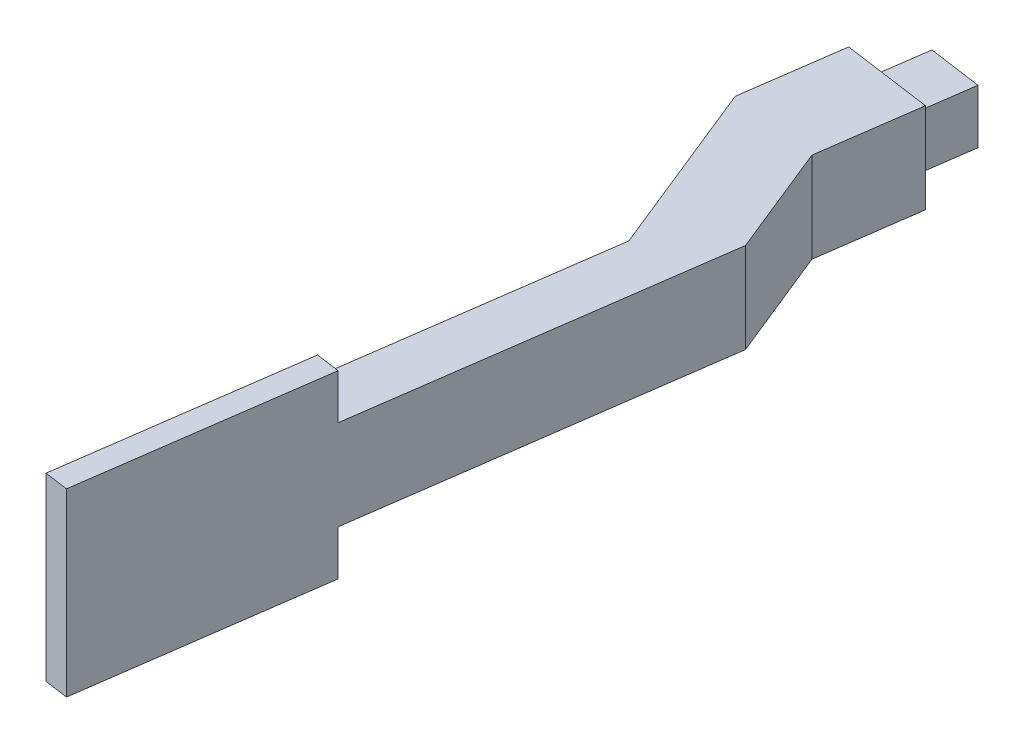
SolidWorks part; units mm, degrees
ref_plane "Plan de face" through (0, 0, 0) normal (0, 0, 1) x (1, 0, 0)
ref_plane "Plan de dessus" through (0, 0, 0) normal (0, 1, 0) x (1, 0, 0)
ref_plane "Plan de droite" through (0, 0, 0) normal (1, 0, 0) x (0, 0, -1)
sketch "Esquisse2" plane through (0, 0, 0) normal (0, 1, 0) x (1, 0, 0)
  circle A0 centre (0, 0) radius 20
  dimension "D1" = 40
extrude "Boss.-Extru.1" add sketch "Esquisse2" along normal blind 5
sketch "Esquisse3" plane through (0, 5, 0) normal (0, 1, 0) x (1, 0, 0)
  line L0 (-1.625, 19.9339) -> (-1.25, 21.9339)
  line L1 (1.25, 21.9339) -> (1.625, 19.9339)
  line L2 (1.625, 19.9339) -> (-1.625, 19.9339)
  line L3 (-1.25, 21.9339) -> (1.25, 21.9339)
  circle A0 centre (0, 0) radius 20 construction
  point P9 (0, 21.9339)
  dimension "2.25" = 2.5
  dimension "D2" = 3.25
  dimension "D3" = 2
extrude "Boss.-Extru.2" add sketch "Esquisse3" against normal blind 5
sketch "Esquisse4" plane through (0, 0, 0) normal (1, 0, 0) x (0, 0, -1)
  line L0 (0, 6.9677) -> (0, -6.1769) construction
  dimension "D1" = 13.1446
ref_plane "Plan1" through (0, 0, 0) normal (0.9903, 0, 0.1392) x (0, -1, 0)
pattern_circular "Répétition circulaire1" count 24 over 360 about axis through (0, 0, 0) along (0, 1, 0) of "Boss.-Extru.2"
hole_wizard "Dégagement M22" positions "Esquisse8" profile "Esquisse9" size "M2" standard "Ansi Metric" slot yes end condition through all
sketch "Esquisse8" plane through (0, 5, 0) normal (0, 1, 0) x (1, 0, 0)
  point P0 (0, 0)
sketch "Esquisse9" plane through (0, 5, 0) normal (1, 0, 0) x (0, 0, 1)
  line L0 (0, 0) -> (0, 5)
  line L1 (0, 5) -> (2.55, 5)
  line L2 (2.55, 5) -> (2.55, 0)
  line L5 (2.55, 0) -> (0, 0)
  line L11 (0, -6.35) -> (0, 107.95) construction
  dimension "Diamètre du perçage jusqu'au prochain" = 5.1
  dimension "Profondeur du perçage jusqu'au prochain" = 5
sketch "Esquisse11" plane through (0, 5, 0) normal (0, 1, 0) x (1, 0, 0)
  line L0 (-5.8011, -14.3321) -> (1.6259, -15.3759)
  line L1 (-5.8011, -14.3321) -> (-7.8887, -29.1861)
  line L2 (1.6259, -15.3759) -> (-0.4617, -30.2299)
  line L3 (-1.895, -44.0211) -> (-7.8887, -29.1861)
  line L4 (-1.0062, -7.1592) -> (1.0062, 7.1592) construction
  line L5 (-0.4617, -30.2299) -> (3.2844, -39.5018)
  line L6 (3.2844, -39.5018) -> (-2.2825, -79.1125)
  line L7 (-2.2825, -79.1125) -> (-6.7388, -78.4862)
  line L8 (-6.7388, -78.4862) -> (-1.895, -44.0211)
  dimension "D1" = 15
  dimension "D2" = 7.5
  dimension "15" = 15
  dimension "D3" = 15
  dimension "D4" = 3.75
  dimension "D5" = 150
  dimension "D6" = 150
  dimension "D7" = 40
  dimension "D8" = 4.5
  dimension "D9" = 5
extrude "Boss.-Extru.3" add sketch "Esquisse11" against normal blind 7.5
sketch "Esquisse13" plane through (3.7135, 0, 0.5219) normal (0.9903, 0, 0.1392) x (0.1392, 0, -0.9903)
  line L1 (-21.6382, 26.561) -> (35.5681, 26.561)
  line L2 (-21.6382, 26.561) -> (-21.6382, -11.2376)
  line L3 (-21.6382, -11.2376) -> (35.5681, -11.2376)
  line L4 (35.5681, 26.561) -> (35.5681, -11.2376)
  line L5 (-21.6382, 5) -> (-21.6382, 0) construction
extrude "Enlèv. mat.-Extru.2" cut sketch "Esquisse13" against normal through all both and the other way through all
sketch "Esquisse14" plane through (-3.0114, 0, 21.4276) normal (0.1392, 0, -0.9903) x (-0.9903, 0, -0.1392)
  line L0 (3.75, 5) -> (-3.75, 5) construction
  line L1 (-2.25, 3.5) -> (2.25, 3.5)
  line L2 (-2.25, 3.5) -> (-2.25, -1)
  line L3 (-2.25, -1) -> (2.25, -1)
  line L4 (2.25, 3.5) -> (2.25, -1)
  line L5 (-3.75, -2.5) -> (3.75, -2.5) construction
  line L6 (3.75, 5) -> (3.75, -2.5) construction
  line L7 (-3.75, -2.5) -> (-3.75, 5) construction
  dimension "D1" = 1.5
  dimension "D2" = 1.5
  dimension "D3" = 1.5
  dimension "D4" = 1.5
extrude "Boss.-Extru.5" add sketch "Esquisse14" along normal blind 5
sketch "Esquisse17" plane through (8.6648, 0, 1.2178) normal (0.9903, 0, 0.1392) x (0.1392, 0, -0.9903)
  line L0 (-78.6603, -2.5) -> (-78.6603, 5) construction
  line L1 (-68.6603, 8.75) -> (-88.6603, 8.75)
  line L2 (-68.6603, 8.75) -> (-68.6603, -6.25)
  line L3 (-68.6603, -6.25) -> (-88.6603, -6.25)
  line L4 (-88.6603, 8.75) -> (-88.6603, -6.25)
  point P4 (-78.6603, -6.25)
  point P7 (-78.6603, 1.25)
  point P8 (-68.6603, 1.25)
  dimension "D1" = 10
  dimension "D2" = 15
  dimension "D3" = 10
extrude "Boss.-Extru.7" add sketch "Esquisse17" against normal blind 2
fillet "Congé1" radius 2 3 edges at (-4.2631, 1.25, 78.8342) (-3.5672, -2.5, 73.8828) (-3.5672, 5, 73.8828)
fillet "Congé2" radius 2 1 edges at (-6.7388, 1.25, 78.4862)
